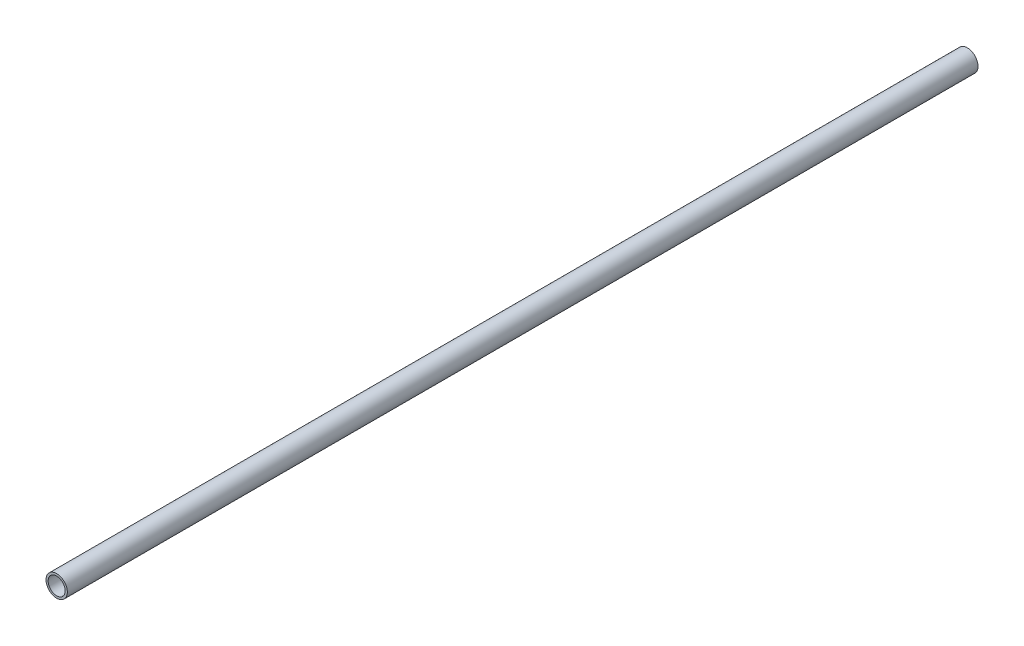
SolidWorks part; units mm, degrees
ref_plane "Front Plane" through (0, 0, 0) normal (0, 0, 1) x (1, 0, 0)
ref_plane "Top Plane" through (0, 0, 0) normal (0, 1, 0) x (1, 0, 0)
ref_plane "Right Plane" through (0, 0, 0) normal (1, 0, 0) x (0, 0, -1)
sketch "Sketch1" plane through (0, 0, 0) normal (0, 1, 0) x (1, 0, 0)
  line L0 (0, 0) -> (640, 0) construction
  line L1 (0, 0) -> (591.2829, 244.9174)
  line L2 (0, 0) -> (591.2829, -244.9174)
  line L3 (0, 0) -> (244.9174, -591.2829)
  line L4 (0, 0) -> (-244.9174, -591.2829)
  line L5 (0, 0) -> (-591.2829, -244.9174)
  line L6 (0, 0) -> (-591.2829, 244.9174)
  line L7 (0, 0) -> (-244.9174, 591.2829)
  line L8 (0, 0) -> (244.9174, 591.2829)
  line L9 (0, 145) -> (55, 145) construction
  line L10 (0, 0) -> (100, 0) construction
  line L11 (0, 0) -> (0, 145) construction
  line L14 (100, 0) -> (100, 145) construction
  circle A0 centre (0, 0) radius 640 construction
  point P15 (0, 0)
  dimension "D1" = 1280
  dimension "D2" = 22.5
  dimension "D4" = 145
  dimension "D5" = 100
  dimension "D6" = 55
  dimension "D3" = 8
sketch "Sketch2" plane through (0, 0, 0) normal (0, 1, 0) x (1, 0, 0)
  line L0 (-486.9956, 169.5033) -> (-66.9956, 169.5033) construction
  line L1 (-188.7141, -86.1278) -> (-188.7141, 241.8722) construction
  line L2 (525.6625, -1048.8053) -> (466.9027, -726.1115) construction
sketch "Sketch3" plane through (0, 0, 0) normal (0, 1, 0) x (1, 0, 0)
  line L0 (0, 0) -> (381.2468, 0) construction
  line L5 (0, 0) -> (0, 199.4415) construction
  line L6 (-10.2736, 158.9263) -> (10.2736, 158.9263)
  line L7 (10.2736, 158.9263) -> (13.1995, 163.9003)
  line L8 (13.1995, 163.9003) -> (45.5131, 148.2994)
  line L9 (45.5131, 148.2994) -> (66.2904, 80.9335)
  line L10 (66.2904, 80.9335) -> (73.8622, 80.9335)
  line L11 (73.8622, 80.9335) -> (86.8684, 42.4396)
  line L12 (86.8684, 42.4396) -> (86.8684, 30.0712)
  line L13 (86.8684, 30.0712) -> (81.3965, 24.5993)
  line L14 (81.3965, 24.5993) -> (81.3965, -24.5993)
  line L15 (-5.8349, 67.4929) -> (5.8349, 67.4929) construction
  line L16 (16.6008, 64.1674) -> (16.6008, 27.6557) construction
  line L17 (16.6008, 27.6557) -> (13.2646, 22.809) construction
  line L18 (13.2646, 22.809) -> (13.2646, -22.809) construction
  line L19 (5.8349, 128.0146) -> (5.8349, 107.4452)
  line L22 (5.8349, 107.4452) -> (9.2702, 107.4452)
  line L25 (9.2702, 107.4452) -> (10.663, 103.7163)
  line L26 (10.663, 103.7163) -> (20.7578, 101.0699)
  line L27 (20.7578, 101.0699) -> (32.199, 111.7601)
  line L28 (32.199, 111.7601) -> (32.199, 123.5038)
  line L29 (32.199, 123.5038) -> (24.9078, 123.5038)
  line L30 (24.9078, 123.5038) -> (13.8412, 132.5856)
  line L31 (13.8412, 132.5856) -> (9.2702, 132.5856)
  line L32 (9.2702, 132.5856) -> (5.8349, 128.0146)
  line L33 (41.9414, 39.7891) -> (51.4866, 54.1602)
  line L34 (51.4866, 54.1602) -> (55.4027, 54.1602)
  line L35 (55.4027, 54.1602) -> (58.1637, 51.3993)
  line L36 (58.1637, 51.3993) -> (58.1637, 43.1872)
  line L37 (58.1637, 43.1872) -> (66.3555, 28.462)
  line L38 (66.3555, 28.462) -> (66.3555, 24.0728)
  line L39 (66.3555, 24.0728) -> (62.2596, 17.9061)
  line L40 (62.2596, 17.9061) -> (47.8497, 18.1669)
  line L41 (47.8497, 18.1669) -> (41.9414, 27.1878)
  line L42 (41.9414, 27.1878) -> (41.9414, 39.7891)
  line L43 (-41.9414, 27.1878) -> (-41.9414, 39.7891)
  line L44 (-47.8497, 18.1669) -> (-41.9414, 27.1878)
  line L45 (-62.2596, 17.9061) -> (-47.8497, 18.1669)
  line L46 (-66.3555, 24.0728) -> (-62.2596, 17.9061)
  line L47 (-66.3555, 28.462) -> (-66.3555, 24.0728)
  line L48 (-58.1637, 43.1872) -> (-66.3555, 28.462)
  line L49 (-58.1637, 51.3993) -> (-58.1637, 43.1872)
  line L50 (-55.4027, 54.1602) -> (-58.1637, 51.3993)
  line L51 (-51.4866, 54.1602) -> (-55.4027, 54.1602)
  line L52 (-41.9414, 39.7891) -> (-51.4866, 54.1602)
  line L53 (-9.2702, 132.5856) -> (-5.8349, 128.0146)
  line L54 (-13.8412, 132.5856) -> (-9.2702, 132.5856)
  line L55 (-24.9078, 123.5038) -> (-13.8412, 132.5856)
  line L56 (-32.199, 123.5038) -> (-24.9078, 123.5038)
  line L57 (-32.199, 111.7601) -> (-32.199, 123.5038)
  line L58 (-20.7578, 101.0699) -> (-32.199, 111.7601)
  line L59 (-10.663, 103.7163) -> (-20.7578, 101.0699)
  line L60 (-9.2702, 107.4452) -> (-10.663, 103.7163)
  line L61 (-5.8349, 107.4452) -> (-9.2702, 107.4452)
  line L62 (-5.8349, 128.0146) -> (-5.8349, 107.4452)
  line L63 (-13.2646, 22.809) -> (-13.2646, -22.809) construction
  line L64 (-16.6008, 27.6557) -> (-13.2646, 22.809) construction
  line L65 (-16.6008, 64.1674) -> (-16.6008, 27.6557) construction
  line L66 (-81.3965, 24.5993) -> (-81.3965, -24.5993)
  line L67 (-86.8684, 30.0712) -> (-81.3965, 24.5993)
  line L68 (-86.8684, 42.4396) -> (-86.8684, 30.0712)
  line L69 (-73.8622, 80.9335) -> (-86.8684, 42.4396)
  line L70 (-66.2904, 80.9335) -> (-73.8622, 80.9335)
  line L71 (-45.5131, 148.2994) -> (-66.2904, 80.9335)
  line L72 (-13.1995, 163.9003) -> (-45.5131, 148.2994)
  line L73 (-10.2736, 158.9263) -> (-13.1995, 163.9003)
  line L74 (-10.2736, -158.9263) -> (-13.1995, -163.9003)
  line L75 (-13.1995, -163.9003) -> (-45.5131, -148.2994)
  line L76 (-45.5131, -148.2994) -> (-66.2904, -80.9335)
  line L77 (-66.2904, -80.9335) -> (-73.8622, -80.9335)
  line L78 (-73.8622, -80.9335) -> (-86.8684, -42.4396)
  line L79 (-86.8684, -42.4396) -> (-86.8684, -30.0712)
  line L80 (-86.8684, -30.0712) -> (-81.3965, -24.5993)
  line L81 (-16.6008, -64.1674) -> (-16.6008, -27.6557) construction
  line L82 (-16.6008, -27.6557) -> (-13.2646, -22.809) construction
  line L83 (-5.8349, -128.0146) -> (-5.8349, -107.4452)
  line L84 (-5.8349, -107.4452) -> (-9.2702, -107.4452)
  line L85 (-9.2702, -107.4452) -> (-10.663, -103.7163)
  line L86 (-10.663, -103.7163) -> (-20.7578, -101.0699)
  line L87 (-20.7578, -101.0699) -> (-32.199, -111.7601)
  line L88 (-32.199, -111.7601) -> (-32.199, -123.5038)
  line L89 (-32.199, -123.5038) -> (-24.9078, -123.5038)
  line L90 (-24.9078, -123.5038) -> (-13.8412, -132.5856)
  line L91 (-13.8412, -132.5856) -> (-9.2702, -132.5856)
  line L92 (-9.2702, -132.5856) -> (-5.8349, -128.0146)
  line L93 (-41.9414, -39.7891) -> (-51.4866, -54.1602)
  line L94 (-51.4866, -54.1602) -> (-55.4027, -54.1602)
  line L95 (-55.4027, -54.1602) -> (-58.1637, -51.3993)
  line L96 (-58.1637, -51.3993) -> (-58.1637, -43.1872)
  line L97 (-58.1637, -43.1872) -> (-66.3555, -28.462)
  line L98 (-66.3555, -28.462) -> (-66.3555, -24.0728)
  line L99 (-66.3555, -24.0728) -> (-62.2596, -17.9061)
  line L100 (-62.2596, -17.9061) -> (-47.8497, -18.1669)
  line L101 (-47.8497, -18.1669) -> (-41.9414, -27.1878)
  line L102 (-41.9414, -27.1878) -> (-41.9414, -39.7891)
  line L103 (41.9414, -27.1878) -> (41.9414, -39.7891)
  line L104 (47.8497, -18.1669) -> (41.9414, -27.1878)
  line L105 (62.2596, -17.9061) -> (47.8497, -18.1669)
  line L106 (66.3555, -24.0728) -> (62.2596, -17.9061)
  line L107 (66.3555, -28.462) -> (66.3555, -24.0728)
  line L108 (58.1637, -43.1872) -> (66.3555, -28.462)
  line L109 (58.1637, -51.3993) -> (58.1637, -43.1872)
  line L110 (55.4027, -54.1602) -> (58.1637, -51.3993)
  line L111 (51.4866, -54.1602) -> (55.4027, -54.1602)
  line L112 (41.9414, -39.7891) -> (51.4866, -54.1602)
  line L113 (9.2702, -132.5856) -> (5.8349, -128.0146)
  line L114 (13.8412, -132.5856) -> (9.2702, -132.5856)
  line L115 (24.9078, -123.5038) -> (13.8412, -132.5856)
  line L116 (32.199, -123.5038) -> (24.9078, -123.5038)
  line L117 (32.199, -111.7601) -> (32.199, -123.5038)
  line L118 (20.7578, -101.0699) -> (32.199, -111.7601)
  line L119 (10.663, -103.7163) -> (20.7578, -101.0699)
  line L120 (9.2702, -107.4452) -> (10.663, -103.7163)
  line L121 (5.8349, -107.4452) -> (9.2702, -107.4452)
  line L122 (5.8349, -128.0146) -> (5.8349, -107.4452)
  line L123 (16.6008, -27.6557) -> (13.2646, -22.809) construction
  line L124 (16.6008, -64.1674) -> (16.6008, -27.6557) construction
  line L125 (-5.8349, -67.4929) -> (5.8349, -67.4929) construction
  line L126 (86.8684, -30.0712) -> (81.3965, -24.5993)
  line L127 (86.8684, -42.4396) -> (86.8684, -30.0712)
  line L128 (73.8622, -80.9335) -> (86.8684, -42.4396)
  line L129 (66.2904, -80.9335) -> (73.8622, -80.9335)
  line L130 (45.5131, -148.2994) -> (66.2904, -80.9335)
  line L131 (13.1995, -163.9003) -> (45.5131, -148.2994)
  line L132 (10.2736, -158.9263) -> (13.1995, -163.9003)
  line L133 (-10.2736, -158.9263) -> (10.2736, -158.9263)
  line L134 (-5.3457, 68.4929) -> (5.3457, 68.4929)
  line L135 (17.6008, 64.1674) -> (17.6008, 27.3448)
  line L136 (17.6008, 27.3448) -> (14.2646, 22.498)
  line L137 (14.2646, 22.498) -> (14.2646, -22.498)
  line L138 (-17.6008, 64.1674) -> (-17.6008, 27.3448)
  line L139 (-17.6008, 27.3448) -> (-14.2646, 22.498)
  line L140 (-5.3457, 68.4929) -> (5.3457, 68.4929) construction
  line L141 (14.2646, 22.498) -> (14.2646, -22.498) construction
  line L142 (17.6008, -27.3448) -> (14.2646, -22.498) construction
  line L143 (17.6008, -64.1674) -> (17.6008, -27.3448) construction
  line L144 (-14.2646, 22.498) -> (-14.2646, -22.498)
  line L145 (17.6008, -64.1674) -> (17.6008, -27.3448)
  line L146 (17.6008, -27.3448) -> (14.2646, -22.498)
  line L147 (-17.6008, -27.3448) -> (-14.2646, -22.498)
  line L148 (-17.6008, -64.1674) -> (-17.6008, -27.3448)
  line L149 (-5.3457, -68.4929) -> (5.3457, -68.4929)
  arc A0 (5.8349, 67.4929) -> (16.6008, 64.0252) centre (10.663, 64.0364) cw construction
  arc A5 (-5.8349, 67.4929) -> (-16.6008, 64.0252) centre (-10.663, 64.0364) ccw construction
  arc A6 (-5.8349, -67.4929) -> (-16.6008, -64.0252) centre (-10.663, -64.0364) cw construction
  arc A7 (5.8349, -67.4929) -> (16.6008, -64.0252) centre (10.663, -64.0364) ccw construction
  arc A8 (-5.3457, 68.4929) -> (-17.6008, 64.0234) centre (-10.663, 64.0364) ccw
  arc A9 (5.3457, 68.4929) -> (17.6008, 64.0234) centre (10.663, 64.0364) cw
  arc A10 (-5.3457, 68.4929) -> (-17.6008, 64.0234) centre (-10.663, 64.0364) ccw construction
  arc A11 (5.3457, -68.4929) -> (17.6008, -64.0234) centre (10.663, -64.0364) ccw
  arc A12 (-5.3457, -68.4929) -> (-17.6008, -64.0234) centre (-10.663, -64.0364) cw
  ellipse E0 centre (11.3851, 149.6854) end of major axis (12.0553, 155.2702) minor radius 3.0047
  ellipse E1 centre (33.6925, 82.363) end of major axis (41.1096, 88.3895) minor radius 4.3287
  ellipse E2 centre (44.8955, 74.0187) end of major axis (51.4866, 79.374) minor radius 4.6847
  ellipse E3 centre (66.3555, 66.447) end of major axis (67.1471, 72.2416) minor radius 3.5711
  ellipse E4 centre (-66.3555, 66.447) end of major axis (-67.1471, 72.2416) minor radius 3.5711
  ellipse E5 centre (-44.8955, 74.0187) end of major axis (-51.4866, 79.374) minor radius 4.6847
  ellipse E6 centre (-33.6925, 82.363) end of major axis (-41.1096, 88.3895) minor radius 4.3287
  ellipse E7 centre (-11.3851, 149.6854) end of major axis (-12.0553, 155.2702) minor radius 3.0047
  ellipse E8 centre (-11.3851, -149.6854) end of major axis (-12.0553, -155.2702) minor radius 3.0047
  ellipse E9 centre (-33.6925, -82.363) end of major axis (-41.1096, -88.3895) minor radius 4.3287
  ellipse E10 centre (-44.8955, -74.0187) end of major axis (-51.4866, -79.374) minor radius 4.6847
  ellipse E11 centre (-66.3555, -66.447) end of major axis (-67.1471, -72.2416) minor radius 3.5711
  ellipse E12 centre (66.3555, -66.447) end of major axis (67.1471, -72.2416) minor radius 3.5711
  ellipse E13 centre (44.8955, -74.0187) end of major axis (51.4866, -79.374) minor radius 4.6847
  ellipse E14 centre (33.6925, -82.363) end of major axis (41.1096, -88.3895) minor radius 4.3287
  ellipse E15 centre (11.3851, -149.6854) end of major axis (12.0553, -155.2702) minor radius 3.0047
  point P117 (0, 67.4929)
  point P126 (0, 158.9263)
  point P180 (0, -158.9263)
  point P181 (0, -67.4929)
  point P190 (-81.3965, 0)
  point P193 (-13.2646, 0)
  point P234 (13.2646, 0)
  point P237 (81.3965, 0)
  point P261 (0, 68.4929)
  point P271 (14.2646, 0)
  point P274 (-14.2646, 0)
  dimension "D1" = 1
sketch "Sketch4" plane through (0, 0, 0) normal (0, 1, 0) x (1, 0, 0)
  line L0 (0, 0) -> (81.2255, 0) construction
  line L1 (0, 0) -> (0, 97.3086) construction
  line L2 (0, 0) -> (0, 199.4415) construction
  line L3 (-10.1399, 86.6928) -> (10.1399, 86.6928)
  line L4 (10.1399, 86.6928) -> (16.0235, 80.8091)
  line L5 (16.0235, 80.8091) -> (23.9736, 57.3032)
  line L6 (23.9736, 57.3032) -> (23.9736, 47.8894)
  line L7 (23.9736, 47.8894) -> (21.6776, 47.8894)
  line L8 (21.6776, 47.8894) -> (21.6776, 27.2256)
  line L9 (21.6776, 27.2256) -> (27.5382, 22.1416)
  line L10 (27.5382, 22.1416) -> (27.5382, 14.9676)
  line L11 (27.5382, 14.9676) -> (23.9736, 10.8585)
  line L12 (23.9736, 10.8585) -> (23.9736, -10.8585)
  line L13 (-23.9736, 10.8585) -> (-23.9736, -10.8585)
  line L14 (-27.5382, 14.9676) -> (-23.9736, 10.8585)
  line L15 (-27.5382, 22.1416) -> (-27.5382, 14.9676)
  line L16 (-21.6776, 27.2256) -> (-27.5382, 22.1416)
  line L17 (-21.6776, 47.8894) -> (-21.6776, 27.2256)
  line L18 (-23.9736, 47.8894) -> (-21.6776, 47.8894)
  line L19 (-23.9736, 57.3032) -> (-23.9736, 47.8894)
  line L20 (-16.0235, 80.8091) -> (-23.9736, 57.3032)
  line L21 (-10.1399, 86.6928) -> (-16.0235, 80.8091)
  line L22 (-10.1399, -86.6928) -> (-16.0235, -80.8091)
  line L23 (-16.0235, -80.8091) -> (-23.9736, -57.3032)
  line L24 (-23.9736, -57.3032) -> (-23.9736, -47.8894)
  line L25 (-23.9736, -47.8894) -> (-21.6776, -47.8894)
  line L26 (-21.6776, -47.8894) -> (-21.6776, -27.2256)
  line L27 (-21.6776, -27.2256) -> (-27.5382, -22.1416)
  line L28 (-27.5382, -22.1416) -> (-27.5382, -14.9676)
  line L29 (-27.5382, -14.9676) -> (-23.9736, -10.8585)
  line L30 (27.5382, -14.9676) -> (23.9736, -10.8585)
  line L31 (27.5382, -22.1416) -> (27.5382, -14.9676)
  line L32 (21.6776, -27.2256) -> (27.5382, -22.1416)
  line L33 (21.6776, -47.8894) -> (21.6776, -27.2256)
  line L34 (23.9736, -47.8894) -> (21.6776, -47.8894)
  line L35 (23.9736, -57.3032) -> (23.9736, -47.8894)
  line L36 (16.0235, -80.8091) -> (23.9736, -57.3032)
  line L37 (10.1399, -86.6928) -> (16.0235, -80.8091)
  line L38 (-10.1399, -86.6928) -> (10.1399, -86.6928)
  point P3 (0, -86.6928)
  point P27 (0, 86.6928)
  point P37 (-23.9736, 0)
  point P38 (23.9736, 0)
sketch "Sketch5" plane through (0, 0, 0) normal (0, 1, 0) x (1, 0, 0)
  line L0 (0, 68.4929) -> (0, 86.6928) construction
  line L1 (15.4511, 110) -> (223.3697, 546.0887)
  line L2 (0, 0) -> (0, 251.8084) construction
  line L3 (0, 110) -> (47.9221, 110) construction
  line L5 (244.9174, 616.9519) -> (262.4572, 609.0616) construction
  line L6 (262.4572, 609.0616) -> (269.1565, 599.6825) construction
  line L7 (269.1565, 599.6825) -> (256.4381, 571.4103) construction
  line L8 (256.4381, 571.4103) -> (244.9174, 563.1812) construction
  line L9 (244.9174, 563.1812) -> (221.08, 517.0826) construction
  line L10 (221.08, 517.0826) -> (201.6817, 527.1134) construction
  line L11 (201.6817, 527.1134) -> (221.6088, 571.4103) construction
  line L12 (221.6088, 571.4103) -> (218.2415, 584.6462) construction
  line L13 (218.2415, 584.6462) -> (232.4366, 616.2011) construction
  line L14 (232.4366, 616.2011) -> (244.9174, 616.9519) construction
  line L15 (244.9174, 591.2829) -> (309.3694, 564.586) construction
  line L16 (269.6266, 526.9284) -> (173.6132, 566.6985) construction
  line L18 (0, 0) -> (107.3069, 0) construction
  dimension "D1" = 110
  dimension "D2" = 50
sketch "Sketch6" plane through (0, 0, 0) normal (0, 1, 0) x (1, 0, 0)
  line L1 (27.9119, 24.7148) -> (544.6401, 226.6863)
  circle A0 centre (0, 0) radius 640 construction
  circle A1 centre (0, 0) radius 640 construction
  circle A3 centre (0, 0) radius 589.9318 construction
  dimension "D1" = 50.0682
sketch "Sketch19" plane through (0, 0, 0) normal (0, 1, 0) x (1, 0, 0)
  line L0 (128.4599, 309.2664) -> (271.805, 137.4916)
  line L5 (26.7343, 104.6204) -> (234.6528, 540.7091)
  line L6 (26.7343, 104.6204) -> (234.6528, 540.7091) construction
  line L7 (4.1679, 115.3796) -> (212.0865, 551.4683)
  line L8 (4.1679, 115.3796) -> (212.0865, 551.4683) construction
  line L9 (20.631, 43.3425) -> (537.3592, 245.3139)
  line L10 (32.4624, 13.0726) -> (549.1907, 215.044)
  line L11 (32.4624, 13.0726) -> (549.1907, 215.044) construction
  line L12 (23.3613, 36.3571) -> (540.0895, 238.3286)
  line L13 (23.3613, 36.3571) -> (540.0895, 238.3286) construction
  line L14 (20.631, 43.3425) -> (537.3592, 245.3139) construction
  line L15 (30.1192, 103.0065) -> (238.0378, 539.0952)
  line L16 (30.1192, 103.0065) -> (238.0378, 539.0952) construction
  line L22 (21.9961, 39.8498) -> (538.7244, 241.8213)
  line L23 (21.9961, 39.8498) -> (538.7244, 241.8213) construction
  line L24 (33.5042, 101.3926) -> (241.4227, 537.4813)
  line L25 (33.5042, 101.3926) -> (241.4227, 537.4813) construction
  dimension "D1" = 12.5
  dimension "D2" = 12.5
  dimension "D3" = 12.5
  dimension "D4" = 12.5
  dimension "D5" = 16.25
  dimension "D8" = 16.25
  dimension "D10" = 20
  dimension "D11" = 20
sketch "Sketch31" plane through (0, 0, 0) normal (0, 1, 0) x (1, 0, 0)
  line L0 (15.4511, 110) -> (223.3697, 546.0887) construction
  line L1 (27.9119, 24.7148) -> (544.6401, 226.6863) construction
  line L2 (15.4511, 110) -> (223.3697, 546.0887)
  line L3 (27.9119, 24.7148) -> (544.6401, 226.6863)
  line L4 (0, 0) -> (341.2388, 0) construction
  line L5 (0, 0) -> (0, 243.9729) construction
  line L6 (0, 0) -> (0, 251.8084) construction
  line L7 (128.4599, 309.2664) -> (271.805, 137.4916) construction
  line L8 (128.4599, 309.2664) -> (271.805, 137.4916)
  line L9 (27.9119, -24.7148) -> (544.6401, -226.6863)
  line L10 (128.4599, -309.2664) -> (271.805, -137.4916)
  line L11 (15.4511, -110) -> (223.3697, -546.0887)
  line L12 (-15.4511, 110) -> (-223.3697, 546.0887)
  line L13 (-128.4599, 309.2664) -> (-271.805, 137.4916)
  line L14 (-27.9119, 24.7148) -> (-544.6401, 226.6863)
  line L15 (-15.4511, -110) -> (-223.3697, -546.0887)
  line L16 (-128.4599, -309.2664) -> (-271.805, -137.4916)
  line L17 (-27.9119, -24.7148) -> (-544.6401, -226.6863)
  line L19 (-200.1324, -223.379) -> (200.1324, -223.379)
  line L20 (-200.1324, -223.379) -> (-200.1324, 223.379)
  line L21 (-200.1324, 223.379) -> (200.1324, 223.379)
  line L22 (200.1324, -223.379) -> (200.1324, 223.379)
sketch "Sketch32" plane through (0, 0, 0) normal (0, 1, 0) x (1, 0, 0)
  line L0 (200.1324, -223.379) -> (200.1324, 223.379) construction
  line L1 (200.1324, -213.379) -> (200.1324, 213.379)
  line L2 (126.6886, 223.379) -> (273.5763, 223.379) construction
  line L3 (126.6886, 213.379) -> (273.5763, 213.379) construction
  line L4 (107.5254, -223.379) -> (292.7395, -223.379) construction
  line L5 (107.5254, -213.379) -> (292.7395, -213.379) construction
  point P5 (200.1324, 223.379)
  point P10 (200.1324, -223.379)
  dimension "D1" = 10
  dimension "D2" = 10
sweep "Sweep1" add path "Sketch32" circular profile diameter 10 parameters "D3"=10
sweep "Cut-Sweep1" cut path "Sketch32<2>" circular profile diameter 8 parameters "D3"=8
sketch "Sketch32<2>" plane through (0, 0, 0) normal (0, 1, 0) x (1, 0, 0) same geometry as "Sketch32"
